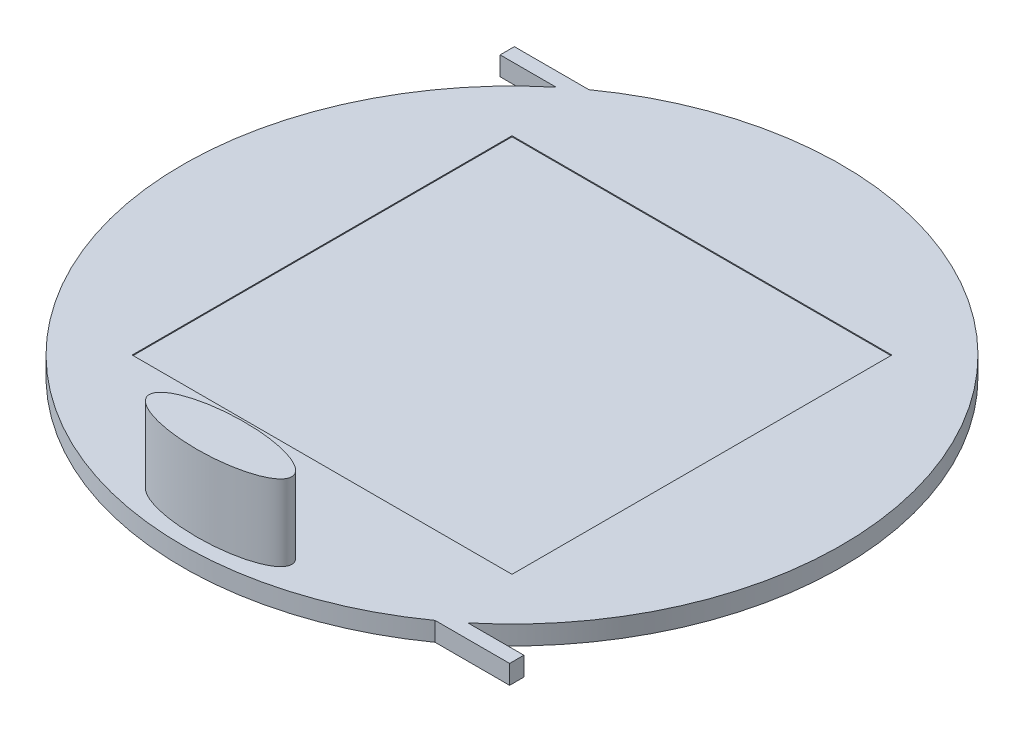
SolidWorks part; units mm, degrees
ref_plane "Front Plane" through (0, 0, 0) normal (0, 0, 1) x (1, 0, 0)
ref_plane "Top Plane" through (0, 0, 0) normal (0, 1, 0) x (1, 0, 0)
ref_plane "Right Plane" through (0, 0, 0) normal (1, 0, 0) x (0, 0, -1)
sketch "Sketch1" plane through (0, 0, 0) normal (0, 1, 0) x (1, 0, 0)
  line L0 (-2.5, -2) -> (2.5, -2) construction
  line L1 (2.5, -2) -> (0, 5) construction
  line L2 (0, 5) -> (-2.5, -2) construction
  line L3 (0, 0) -> (0, -2) construction
  line L4 (0, 5.7433) -> (-2.8548, -2.25)
  line L5 (-2.8548, -2.25) -> (2.8548, -2.25)
  line L6 (2.8548, -2.25) -> (0, 5.7433)
  line L7 (-33.0599, 10.5419) -> (-33.0599, -10.5419)
  line L8 (0, 27.5) -> (0, -27.5) construction
  line L9 (0, 27.5) -> (-28, 27.5)
  line L10 (0, -27.5) -> (28, -27.5)
  circle A0 centre (0, 0) radius 35 construction
  circle A1 centre (0, 0) radius 34.7
  dimension "D1" = 70
  dimension "D3" = 7
  dimension "D4" = 5
  dimension "D5" = 2
  dimension "D7" = 55
  dimension "D8" = 28
  dimension "D2" = 0.3
  dimension "D6" = 0.25
extrude "Boss-Extrude1" add sketch "Sketch1" along normal blind 2 contours L5 L6 L4 | A1 L6 L5 L4 | L7 A1 region at (0, 0, -0.4144) region at (-27.612, 0, -19.3725) region at (-33.7173, 0, 0)
sketch "Sketch3" plane through (0, 2, 0) normal (0, 1, 0) x (1, 0, 0)
  line L0 (-7.5, -30.6947) -> (7.5, -30.6947) construction
  ellipse E0 centre (0, -30.6947) end of major axis (7.5, -30.6947) minor radius 2.5
  dimension "D1" = 5
  dimension "D2" = 15
extrude "Boss-Extrude2" add sketch "Sketch3" along normal blind 8
sketch "Sketch4" plane through (0, 2, 0) normal (0, 1, 0) x (1, 0, 0)
  line L1 (-20, 20) -> (20, 20)
  line L2 (-20, 20) -> (-20, -20)
  line L3 (-20, -20) -> (20, -20)
  line L4 (20, 20) -> (20, -20)
  line L5 (-20, 20) -> (20, -20) construction
  line L6 (-20, -20) -> (20, 20) construction
  point P0 (0, 0)
  dimension "D1" = 40
extrude "Cut-Extrude3" cut sketch "Sketch4" against normal blind 0.1
sketch "Sketch7" plane through (0, 0, 0) normal (0, 0, 1) x (1, 0, 0)
  line L0 (-34.7, 1) -> (-29.75, 0)
  line L1 (-34.7, 2) -> (-34.7, 0) construction
  line L2 (-34.7, 0) -> (34.7, 0) construction
  line L3 (-29.75, 0) -> (-34.7, 0)
  line L4 (-34.7, 0) -> (-34.7, 1)
extrude "Cut-Extrude4" cut sketch "Sketch7" against normal blind 21 and the other way blind 22 contours L3 L4 L0
extrude "Extrude-Thin1" add sketch "Sketch1<6>" along normal blind 2 thin contours L9 | L10 thin type mid plane wall 1.5
sketch "Sketch1<6>" plane through (0, 0, 0) normal (0, 1, 0) x (1, 0, 0) same geometry as "Sketch1"
